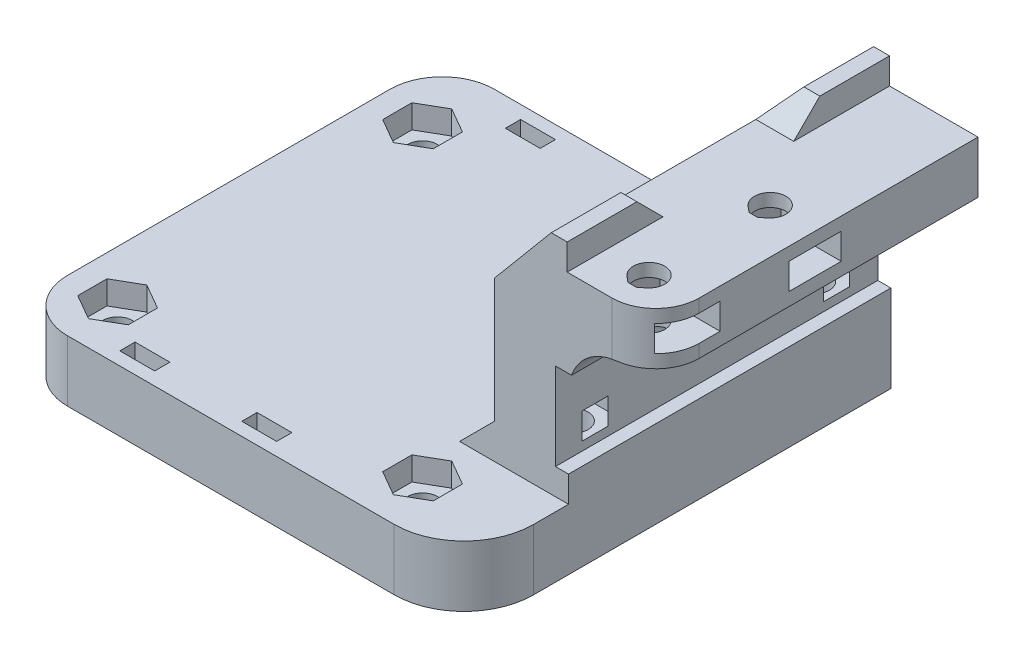
SolidWorks part; units mm, degrees
ref_plane "Alzado" through (0, 0, 0) normal (0, 0, 1) x (1, 0, 0)
ref_plane "Planta" through (0, 0, 0) normal (0, 1, 0) x (1, 0, 0)
ref_plane "Vista lateral" through (0, 0, 0) normal (1, 0, 0) x (0, 0, -1)
sketch "Croquis16" plane through (0, 0, 0) normal (0, 1, 0) x (1, 0, 0)
  line L1 (-23, 24.5) -> (28.5, 24.5)
  line L2 (-23, 24.5) -> (-23, -24.5)
  line L3 (-23, -24.5) -> (28.5, -24.5)
  line L4 (28.5, 24.5) -> (28.5, -24.5)
  line L5 (0, 24.5) -> (0, -24.5) construction
  line L7 (24.5, 24.5) -> (24.5, -24.5) construction
  line L8 (12.5, 12.5) -> (-12.5, -12.5) construction
  line L9 (12.5, -12.5) -> (-12.5, -12.5) construction
  line L10 (12.5, -12.5) -> (12.5, 12.5) construction
  line L11 (12.5, 12.5) -> (-12.5, 12.5) construction
  line L12 (-12.5, -12.5) -> (-12.5, 12.5) construction
  line L13 (-17.5, 16.75) -> (17.5, 16.75) construction
  line L14 (-17.5, 16.75) -> (-17.5, -18.25) construction
  line L15 (-17.5, -18.25) -> (17.5, -18.25) construction
  line L16 (17.5, 16.75) -> (17.5, -18.25) construction
  circle A0 centre (-17.5, 16.75) radius 1.75 construction
  circle A1 centre (17.5, 16.75) radius 1.75 construction
  circle A2 centre (17.5, -18.25) radius 1.75 construction
  circle A3 centre (-17.5, -18.25) radius 1.75 construction
  dimension "D2" = 35
  dimension "D3" = 3.5
  dimension "D4" = 25
  dimension "D5" = 4
  dimension "D6" = 49
  dimension "D8" = 7.75
  dimension "D1" = 28.5
  dimension "D7" = 35
  dimension "D9" = 23
extrude "Saliente-Extruir3" add sketch "Croquis16" along normal blind 7 separate body
sketch "Croquis17" plane through (0, 0, -24.5) normal (0, 0, 1) x (1, 0, 0)
  line L0 (38.5, 30) -> (38.5, 24)
  line L1 (38.5, 24) -> (28.5, 24)
  line L2 (28.5, 24) -> (28.5, 7)
  line L3 (-23, 7) -> (28.5, 7) construction
  line L5 (38.5, 30) -> (20, 30)
  line L6 (20, 30) -> (20, 7)
  line L7 (20, 7) -> (28.5, 7)
  dimension "D1" = 20
  dimension "D2" = 23
  dimension "D3" = 10
  dimension "D5" = 6
extrude "Saliente-Extruir4" add sketch "Croquis17" along normal blind 37
hole_wizard "Taladro de margen para M31" positions "Croquis20" profile "Croquis19" hole size "M3" standard "Iso" end condition through all
sketch "Croquis20" plane through (0, 7, 0) normal (0, 1, 0) x (1, 0, 0)
  point P0 (-17.5, 16.75)
  point P6 (17.5, -18.25)
  point P9 (-17.5, -18.25)
sketch "Croquis19" plane through (-17.5, 7, -16.75) normal (1, 0, 0) x (0, 0, 1)
  line L0 (0, 0) -> (0, 7)
  line L1 (0, 7) -> (1.7, 7)
  line L2 (1.7, 7) -> (1.7, 0)
  line L5 (1.7, 0) -> (0, 0)
  line L11 (0, -6.35) -> (0, 107.95) construction
  dimension "Diámetro de taladro hasta el siguiente" = 3.4
  dimension "Profundidad de taladro hasta el siguiente" = 7
sketch "Croquis23" plane through (0, 7, 0) normal (0, 1, 0) x (1, 0, 0)
  circle A0 centre (0, -12) radius 5
  dimension "D1" = 17
  dimension "D2" = 10
extrude "Cortar-Extruir13" [suppressed] cut sketch "Croquis23" against normal through all
fillet "Redondeo1" radius 6 2 edges at (-23, 3.5, 24.5) (-23, 3.5, -24.5)
fillet "Redondeo2" radius 8 1 edges at (28.5, 3.5, 24.5)
sketch "Croquis24" plane through (0, 7, 0) normal (0, 1, 0) x (1, 0, 0)
  line L0 (-17.5, -21.5986) -> (-14.6, -19.9243)
  line L1 (17.5, -21.5986) -> (20.4, -19.9243)
  line L2 (20.4, -19.9243) -> (20.4, -16.5757)
  line L3 (20.4, -16.5757) -> (17.5, -14.9014)
  line L4 (17.5, -14.9014) -> (14.6, -16.5757)
  line L5 (14.6, -16.5757) -> (14.6, -19.9243)
  line L6 (14.6, -19.9243) -> (17.5, -21.5986)
  line L7 (-20.4, -19.9243) -> (-17.5, -21.5986)
  line L8 (-17.5, -14.9014) -> (-20.4, -16.5757)
  line L9 (-14.6, -19.9243) -> (-14.6, -16.5757)
  line L10 (-20.4, -16.5757) -> (-20.4, -19.9243)
  line L11 (-14.6, -16.5757) -> (-17.5, -14.9014)
  line L12 (-17.5, 20.0986) -> (-20.4, 18.4243)
  line L13 (-14.6, 15.0757) -> (-14.6, 18.4243)
  line L14 (-20.4, 18.4243) -> (-20.4, 15.0757)
  line L15 (-14.6, 18.4243) -> (-17.5, 20.0986)
  line L16 (-17.5, 13.4014) -> (-14.6, 15.0757)
  line L17 (-20.4, 15.0757) -> (-17.5, 13.4014)
  circle A0 centre (17.5, -18.25) radius 2.9 construction
  circle A1 centre (-17.5, -18.25) radius 2.9 construction
  circle A2 centre (-17.5, 16.75) radius 2.9 construction
  dimension "D1" = 5.8
  dimension "D2" = 5.8
extrude "Cortar-Extruir14" cut sketch "Croquis24" against normal offset from surface (2.7 mm away) 4.3 up to face at (-17.5, 0, -15.05)
fillet "Redondeo3" radius 6 1 edges at (28.5, 24, -6)
sketch "Croquis21" plane through (0, 30, 0) normal (0, 1, 0) x (1, 0, 0)
  line L0 (34.507, 4.4211) -> (33.85, 3.8698)
  line L1 (38.5, 24.5) -> (20, 24.5) construction
  line L2 (33.85, 3.8698) -> (32.85, 3.8698)
  line L3 (38.5, 5.8) -> (20, 5.8) construction
  line L4 (38.5, -12.5) -> (38.5, 24.5) construction
  line L5 (32.85, 3.8698) -> (32.193, 4.4211)
  line L6 (20, -12.5) -> (20, 24.5) construction
  line L7 (33.35, 5.8) -> (33.35, 3.8698) construction
  line L9 (33.85, -10.0352) -> (32.85, -10.0352)
  line L10 (32.85, -10.0352) -> (32.193, -9.4839)
  line L11 (34.507, -9.4839) -> (33.85, -10.0352)
  arc A0 (34.507, 4.4211) -> (32.193, 4.4211) centre (33.35, 5.8) ccw
  arc A1 (34.507, -9.4839) -> (32.193, -9.4839) centre (33.35, -8.105) ccw
  point P1 (33.35, -8.105)
  dimension "D1" = 18.7
  dimension "D2" = 13.35
  dimension "D3" = 3.6
  dimension "D4" = 100
  dimension "D5" = 1
  dimension "D7" = 8.105
extrude "Cortar-Extruir12" cut sketch "Croquis21" against normal through all
fillet "Redondeo10" [suppressed] radius 5
fillet "Redondeo8" [suppressed] radius 10
fillet "Redondeo11" radius 5 1 edges at (38.5, 27, 12.5)
sketch "Croquis26" plane through (0, 0, -24.5) normal (0, 0, -1) x (-1, 0, 0)
  line L0 (-20, 11) -> (-16, 7)
  line L2 (-20, 7) -> (17, 7) construction
  line L3 (-16, 7) -> (-20, 7)
  line L4 (-20, 7) -> (-20, 11)
  line L5 (-20, 30) -> (-20, 7) construction
  line L6 (-14.8, 15) -> (-12.8, 15) construction
  line L7 (-14.8, 15) -> (-14.8, 9) construction
  line L8 (-14.8, 9) -> (-12.8, 9) construction
  line L9 (-12.8, 15) -> (-12.8, 9) construction
  dimension "D1" = 5.2
  dimension "D2" = 6
  dimension "D3" = 2
  dimension "D4" = 2
  dimension "D5" = 45
  dimension "D6" = 4
extrude "Saliente-Extruir5" add sketch "Croquis26" against normal up to surface (37 mm away) up to face at (26.4446, 18.5552, 12.5)
chamfer "Chaflán3" distance 4 angle 50 1 edges at (20, 30, -6) first distance on face at (33.35, 30, 8.9648)
sketch "Croquis29" plane through (0, 0, 0) normal (0, -1, 0) x (1, 0, 0)
  line L0 (28.5, -24.5) -> (-17, -24.5) construction
  line L1 (20, 12.5) -> (20, -24.5) construction
  circle A0 centre (24.45, -19.75) radius 1.75
  circle A1 centre (24.45, 7.95) radius 1.75
  dimension "D1" = 4.75
  dimension "D2" = 4.45
  dimension "D3" = 3.5
  dimension "D4" = 27.7
extrude "Cortar-Extruir17" cut sketch "Croquis29" against normal blind 18
ref_plane "Plano1" through (0, 11, 0) normal (0, -1, 0) x (-1, 0, 0)
sketch "Croquis30" plane through (0, 11, 0) normal (0, -1, 0) x (-1, 0, 0)
  line L0 (-22.7468, 16.8) -> (-20, 16.8)
  line L1 (-21.0436, 19.75) -> (-22.7468, 22.7) construction
  line L2 (-22.7468, 22.7) -> (-26.1532, 22.7)
  line L3 (-26.1532, 22.7) -> (-27.8564, 19.75)
  line L4 (-27.8564, 19.75) -> (-26.1532, 16.8)
  line L5 (-26.1532, 16.8) -> (-22.7468, 16.8)
  line L6 (-22.7468, 16.8) -> (-21.0436, 19.75) construction
  line L7 (-20, 16.8) -> (-20, 22.7)
  line L8 (-20, 22.7) -> (-22.7468, 22.7)
  line L10 (-24.45, 19.75) -> (-24.45, -7.95) construction
  line L11 (-20, -12.5) -> (-20, 24.5) construction
  line L12 (-24.45, 5.9) -> (-6.0551, 5.9) construction
  line L13 (-22.7468, -5) -> (-21.0436, -7.95) construction
  line L14 (-21.0436, -7.95) -> (-22.7468, -10.9) construction
  line L15 (-20, -10.9) -> (-22.7468, -10.9)
  line L16 (-20, -5) -> (-20, -10.9)
  line L17 (-26.1532, -5) -> (-22.7468, -5)
  line L18 (-27.8564, -7.95) -> (-26.1532, -5)
  line L19 (-26.1532, -10.9) -> (-27.8564, -7.95)
  line L20 (-22.7468, -10.9) -> (-26.1532, -10.9)
  line L21 (-22.7468, -5) -> (-20, -5)
  circle A0 centre (-24.45, 19.75) radius 2.95 construction
  circle A1 centre (-24.45, -7.95) radius 2.95 construction
  dimension "D1" = 5.9
extrude "Cortar-Extruir18" cut sketch "Croquis30" against normal blind 3
ref_plane "Plano2" through (0, 28.5, 0) normal (0, 1, 0) x (1, 0, 0)
sketch "Croquis25" plane through (0, 28.5, 0) normal (0, -1, 0) x (1, 0, 0)
  line L0 (35.0821, -2.8) -> (38.5, -2.8)
  line L1 (38.5, 7.5) -> (38.5, -24.5) construction
  line L2 (35.0821, -8.8) -> (38.5, -8.8)
  line L4 (38.5, -8.8) -> (38.5, -2.8)
  line L5 (31.6179, 11.105) -> (29.8859, 8.105)
  line L6 (35.0821, 11.105) -> (31.6179, 11.105)
  line L7 (29.8859, -5.8) -> (31.6179, -8.8)
  line L8 (31.6179, -8.8) -> (35.0821, -8.8)
  line L9 (35.0821, -8.8) -> (36.8141, -5.8) construction
  line L10 (36.8141, -5.8) -> (35.0821, -2.8) construction
  line L11 (35.0821, -2.8) -> (31.6179, -2.8)
  line L12 (31.6179, -2.8) -> (29.8859, -5.8)
  line L13 (31.6179, 5.105) -> (35.0821, 5.105)
  line L14 (35.0821, 5.105) -> (40.5, 5.105)
  line L15 (36.8141, 8.105) -> (35.0821, 11.105) construction
  line L16 (35.0821, 5.105) -> (36.8141, 8.105) construction
  line L17 (29.8859, 8.105) -> (31.6179, 5.105)
  line L18 (40.5, 5.105) -> (40.5, 11.105)
  line L19 (35.0821, 11.105) -> (40.5, 11.105)
  circle A0 centre (33.35, 8.105) radius 3 construction
  circle A1 centre (33.35, -5.8) radius 3 construction
  dimension "D1" = 6
extrude "Cortar-Extruir20" cut sketch "Croquis25" along normal blind 3
sketch "Croquis31" plane through (0, 7, 0) normal (0, 1, 0) x (1, 0, 0)
  line L0 (-23, 0) -> (0, 0) construction
  line L1 (5.5, 21.25) -> (1.5, 21.25)
  line L2 (5.5, 21.25) -> (5.5, 23)
  line L3 (5.5, 23) -> (1.5, 23)
  line L4 (1.5, 21.25) -> (1.5, 23)
  line L5 (-23, 18.5) -> (-23, -18.5) construction
  line L6 (16, -12.5) -> (16, 24.5) construction
  line L7 (16, 24.5) -> (-17, 24.5) construction
  line L8 (1.5, -21.25) -> (1.5, -23)
  line L9 (5.5, -23) -> (1.5, -23)
  line L10 (5.5, -21.25) -> (1.5, -21.25)
  line L11 (5.5, -21.25) -> (5.5, -23)
  point P9 (3.5, 21.25)
  dimension "D1" = 1.5
  dimension "D2" = 4
  dimension "D3" = 1.75
  dimension "D4" = 10.5
extrude "Cortar-Extruir21" cut sketch "Croquis31" against normal up to next
ref_plane "Plano3" through (0, 0, -6) normal (0, 0, -1) x (-1, 0, 0)
sketch "Croquis38" plane through (0, 0, -24.5) normal (0, 0, -1) x (-1, 0, 0)
  line L0 (-24, 30) -> (-28.35, 30)
  line L1 (-38.5, 30) -> (-24, 30) construction
  line L2 (-28.35, 30) -> (-28.35, 33)
  line L3 (-26.5173, 33) -> (-24, 30)
  line L4 (-20, 25.233) -> (-24, 30) construction
  line L5 (-33.35, 30) -> (-33.35, 16.1858) construction
  line L6 (-31.55, 30) -> (-35.15, 30) construction
  line L7 (-28.35, 33) -> (-26.5173, 33)
  dimension "D1" = 5
  dimension "D2" = 3
extrude "Saliente-Extruir10" add sketch "Croquis38" against normal blind 8
mirror "Simetría3" about plane through (0, 0, -6) normal (0, 0, -1) of "Saliente-Extruir10"
chamfer "Chaflán7" distance 3 angle 45 2 edges at (26.175, 30, 4.5)
ref_plane "Plano4" through (-3.5, 0, 0) normal (1, 0, 0) x (0, 0, -1)
mirror "Simetría4" about plane through (-3.5, 0, 0) normal (1, 0, 0) of "Cortar-Extruir21"
sketch "Croquis39" plane through (0, 0, -24.5) normal (0, 0, -1) x (-1, 0, 0)
  line L0 (-28.5, 18) -> (-28.5, 0) construction
  line L1 (-28.5, 20) -> (-27, 20)
  line L2 (-28.5, 20) -> (-28.5, 10)
  line L3 (-28.5, 10) -> (-27, 10)
  line L4 (-27, 20) -> (-27, 10)
  line L6 (-28.5, 20) -> (-30, 20)
  line L7 (-28.5, 20) -> (-28.5, 10)
  line L8 (-28.5, 10) -> (-30, 10)
  line L9 (-30, 20) -> (-30, 10)
  arc M11 (-34.5, 24) -> (-28.5, 18) centre (-34.5, 18) cw
  line M12 (-28.5, 18) -> (-28.5, 0)
  dimension "D1" = 10
  dimension "D2" = 4
  dimension "D3" = 1.5
  dimension "D4" = 1.5
extrude "Cortar-Extruir22" cut sketch "Croquis39" against normal blind 40 contours L6 L9 L8 M12 M11 | L4 L1 L2 L3 M12 | L2 L6 M11 region at (27.75, 15, -24.5) region at (28.6024, 19.5029, -24.5) region at (29.2599, 14.9311, -24.5)
